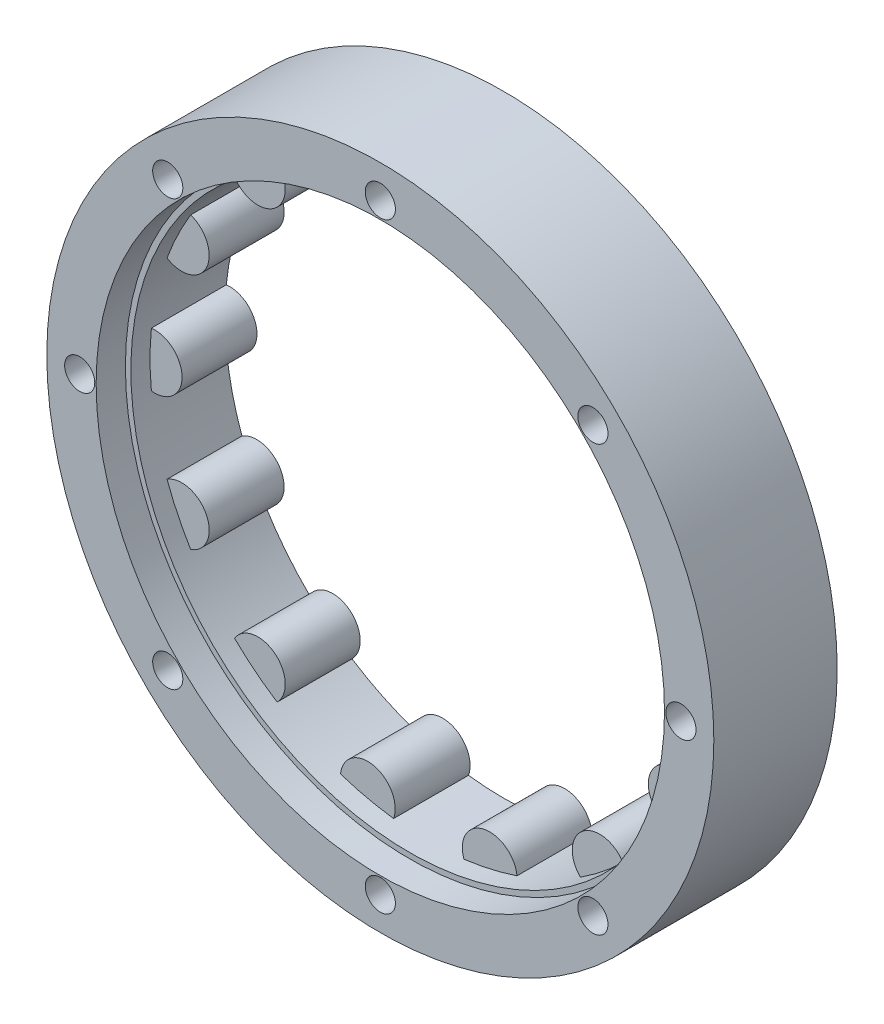
SolidWorks part; units mm, degrees
material "聚脂树脂"
ref_plane "前视基准面" through (0, 0, 0) normal (0, 0, 1) x (1, 0, 0)
ref_plane "上视基准面" through (0, 0, 0) normal (0, 1, 0) x (1, 0, 0)
ref_plane "右视基准面" through (0, 0, 0) normal (1, 0, 0) x (0, 0, -1)
ref_axis "基准轴1" through (0, 0, 55) along (0, 0, -1)
sketch "PinsBaseSketch" plane through (0, 0, 0) normal (0, 0, 1) x (1, 0, 0)
  circle A0 centre (0, 0) radius 33
extrude "PinsBaseExtrude" add sketch "PinsBaseSketch" along normal blind 0.2 and the other way blind 0.2
sketch "PinsSketch" plane through (0, 0, 0) normal (0, 0, 1) x (1, 0, 0)
  circle A0 centre (30, 0) radius 3
extrude "PinsExtrude" add sketch "PinsSketch" along normal blind 8.4 and the other way blind 0.2
pattern_circular "PinsPattern" count 14 every 25.714 about axis through (0, 0, 55) along (0, 0, -1) of "PinsExtrude"
sketch "BoreRevolveSketch" plane through (0, 0, 0) normal (1, 0, 0) x (0, 0, -1)
  line L0 (0, 0) -> (1, 0) construction
  line L1 (-2, 0) -> (2, 0)
  line L2 (2, 0) -> (2, 7.5)
  line L3 (2, 7.5) -> (-2, 7.5)
  line L4 (-2, 7.5) -> (-2, 0)
  dimension "TaperSide1" = 7.5
  dimension "TaperSide2" = 7.5
revolve "BoreRevolveCut" cut sketch "BoreRevolveSketch" angle 360 about L0
sketch "草图4" plane through (0, 0, -0.2) normal (0, 0, -1) x (-1, 0, 0)
  circle A1 centre (0, 0) radius 33
  circle A2 centre (0, 0) radius 33
  dimension "D1" = 0
extrude "切除-拉伸1" cut sketch "草图4" against normal blind 0.4
sketch "草图5" plane through (0, 0, 0.2) normal (0, 0, -1) x (-1, 0, 0)
  circle A0 centre (0, 0) radius 36.5
  circle A1 centre (0, 0) radius 30.5
  dimension "D1" = 73
  dimension "D2" = 61
extrude "凸台-拉伸3" add sketch "草图5" against normal blind 13.5
sketch "草图6" plane through (0, 0, 13.7) normal (0, 0, 1) x (1, 0, 0)
  line L0 (0, 0) -> (32.9, 0)
  circle A0 centre (32.9, 0) radius 1.65
  circle A1 centre (23.2638, -23.2638) radius 1.65
  circle A2 centre (0, -32.9) radius 1.65
  circle A3 centre (-23.2638, -23.2638) radius 1.65
  circle A4 centre (-32.9, 0) radius 1.65
  circle A5 centre (-23.2638, 23.2638) radius 1.65
  circle A6 centre (0, 32.9) radius 1.65
  circle A7 centre (23.2638, 23.2638) radius 1.65
  point P21 (0, 0)
  dimension "D2" = 3.3
  dimension "D1" = 32.9
  dimension "D3" = 8
extrude "切除-拉伸2" cut sketch "草图6" against normal up to next contours A5 | A7 | A0 | A1 | A2 | A6 | A4 | A3 region at (-23.2638, 23.2638, 13.7)
sketch "草图8" plane through (0, 0, 13.7) normal (0, 0, 1) x (1, 0, 0)
  circle A0 centre (0, 0) radius 31.1
  dimension "D1" = 62.2
extrude "切除-拉伸3" cut sketch "草图8" against normal blind 3.2
ref_plane "基准面1" through (0, 0, 13.7) normal (0, 0, 1) x (1, 0, 0)
